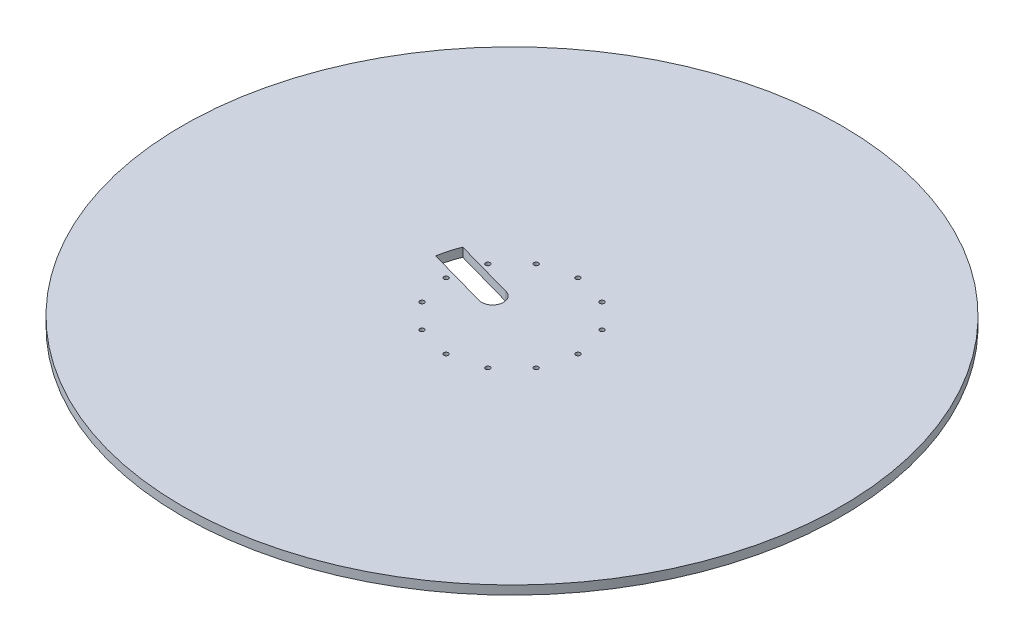
SolidWorks part; units mm, degrees
ref_plane "Front Plane" through (0, 0, 0) normal (0, 0, 1) x (1, 0, 0)
ref_plane "Top Plane" through (0, 0, 0) normal (0, 1, 0) x (1, 0, 0)
ref_plane "Right Plane" through (0, 0, 0) normal (1, 0, 0) x (0, 0, -1)
sketch "Sketch1" plane through (0, 0, 0) normal (0, 1, 0) x (1, 0, 0)
  circle A0 centre (0, 0) radius 300
  circle A1 centre (0, 60) radius 2.05
  circle A9 centre (30, 51.9615) radius 2.05
  circle A10 centre (51.9615, 30) radius 2.05
  circle A11 centre (60, 0) radius 2.05
  circle A12 centre (51.9615, -30) radius 2.05
  circle A13 centre (30, -51.9615) radius 2.05
  circle A14 centre (0, -60) radius 2.05
  circle A15 centre (-30, -51.9615) radius 2.05
  circle A16 centre (-51.9615, -30) radius 2.05
  circle A17 centre (-60, 0) radius 2.05
  circle A18 centre (-51.9615, 30) radius 2.05
  circle A19 centre (-30, 51.9615) radius 2.05
  point P22 (0, 0)
  point P31 (0, 0)
  dimension "D1" = 600
  dimension "D2" = 4.1
  dimension "D3" = 60
  dimension "D4" = 12
extrude "Boss-Extrude1" add sketch "Sketch1" along normal blind 8
sketch "Sketch2" plane through (0, 8, 0) normal (0, 1, 0) x (1, 0, 0)
  line L0 (-17.6224, -5.4497) -> (-82.0396, 12.5895)
  line L1 (-17.6224, -5.4497) -> (-12.2292, 13.8093)
  line L2 (-12.2292, 13.8093) -> (-76.6464, 31.8486)
  line L3 (0, 0) -> (-14.9258, 4.1798) construction
  circle A5 centre (0, 0) radius 75 construction
  arc A6 (-82.0396, 12.5895) -> (-76.6464, 31.8486) centre (0, 0) cw
  dimension "D1" = 150
  dimension "D4" = 8
  dimension "D2" = 15.5
  dimension "D3" = 20
extrude "Cut-Extrude1" cut sketch "Sketch2" against normal through all contours L0 L1 L2 region at (-47.3288, 8, -13.2539)
sketch "Sketch3" plane through (0, 8, 0) normal (0, 1, 0) x (1, 0, 0)
  circle A0 centre (0, 0) radius 75
  dimension "D1" = 150
extrude "Cut-Extrude2" [suppressed] cut sketch "Sketch3" against normal through all flip side to cut
fillet "Fillet1" radius 10 2 edges at (-17.6224, 4, 5.4497) (-12.2292, 4, -13.8093)
